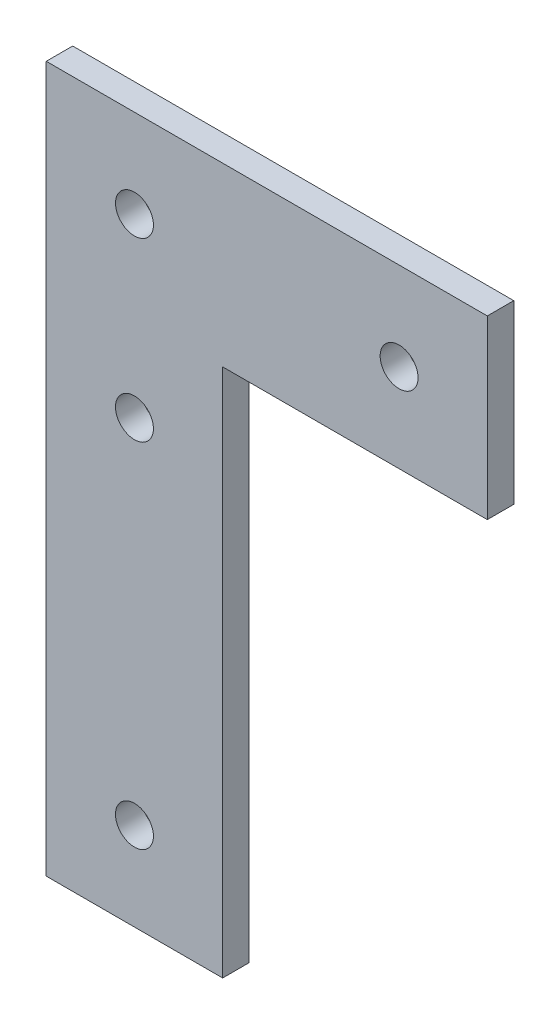
SolidWorks part; units mm, degrees
material "Thornel Mat VMA"
ref_plane "Front Plane" through (0, 0, 0) normal (0, 0, 1) x (1, 0, 0)
ref_plane "Top Plane" through (0, 0, 0) normal (0, 1, 0) x (1, 0, 0)
ref_plane "Right Plane" through (0, 0, 0) normal (1, 0, 0) x (0, 0, -1)
sketch "Sketch1" plane through (0, 0, 0) normal (0, 0, 1) x (1, 0, 0)
  line L0 (-340.6121, 147.905) -> (329.3879, 147.905) construction
  line L1 (-290.6121, 147.905) -> (-340.6121, 147.905)
  line L2 (-290.6121, 147.905) -> (-290.6121, 127.905)
  line L3 (-290.6121, 127.905) -> (-320.6121, 127.905)
  line L4 (-340.6121, 147.905) -> (-340.6121, 127.905)
  line L5 (-340.6121, -492.095) -> (-340.6121, 147.905) construction
  line L6 (-340.6121, 67.905) -> (-340.6121, 147.905) construction
  line L7 (-340.6121, 67.905) -> (-320.6121, 67.905)
  line L8 (-340.6121, 67.905) -> (-340.6121, 127.905)
  line L10 (-320.6121, 67.905) -> (-320.6121, 127.905)
  line L11 (-320.6121, 67.905) -> (-340.6121, 67.905) construction
  line L12 (-290.6121, 147.905) -> (-290.6121, 127.905) construction
  line L13 (-340.6121, 147.905) -> (-290.6121, 147.905) construction
  circle A0 centre (-330.6121, 77.905) radius 2.15 construction
  circle A1 centre (-330.6121, 117.905) radius 2.15 construction
  circle A2 centre (-330.6121, 137.905) radius 2.15 construction
  circle A3 centre (-300.6121, 137.905) radius 2.15 construction
  circle A4 centre (-330.6121, 77.905) radius 2.15
  circle A5 centre (-330.6121, 117.905) radius 2.15
  circle A6 centre (-330.6121, 137.905) radius 2.15
  circle A7 centre (-300.6121, 137.905) radius 2.15
  point P13 (0, 0)
  point P25 (-340.6121, 67.905)
  point P30 (-290.6121, 147.905)
extrude "Extrude1" add sketch "Sketch1" along normal blind 3
